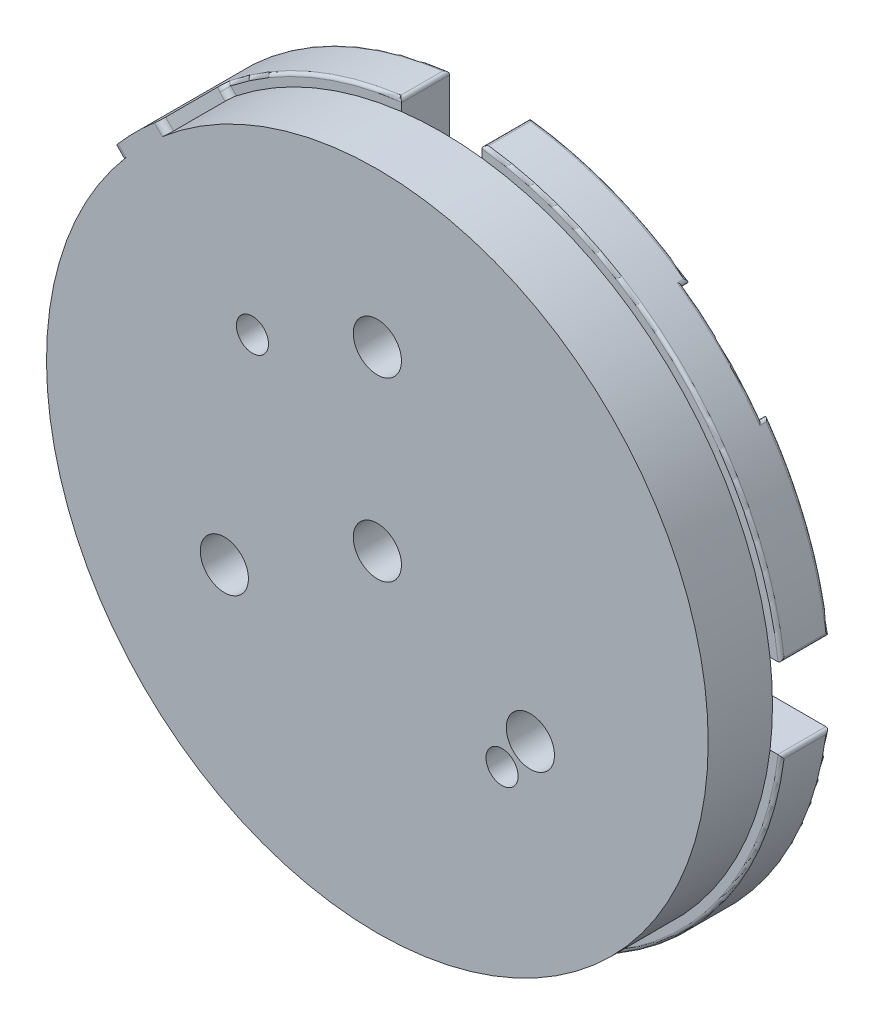
SolidWorks part; units mm, degrees
material "PE High Density"
ref_plane "Front Plane" through (0, 0, 0) normal (0, 0, 1) x (1, 0, 0)
ref_plane "Top Plane" through (0, 0, 0) normal (0, 1, 0) x (1, 0, 0)
ref_plane "Right Plane" through (0, 0, 0) normal (1, 0, 0) x (0, 0, -1)
sketch "Sketch1" plane through (0, 0, 0) normal (0, 0, 1) x (1, 0, 0)
  circle A0 centre (0, 0) radius 10.65
  dimension "D1" = 21.3
extrude "Boss-Extrude1" add sketch "Sketch1" along normal blind 1.5
sketch "Sketch2" plane through (0, 0, 1.5) normal (0, 0, 1) x (1, 0, 0)
  circle A0 centre (0, 0) radius 10.3
  dimension "D1" = 20.6
extrude "Boss-Extrude2" add sketch "Sketch2" along normal blind 2
sketch "Sketch3" plane through (0, 0, 0) normal (0, 0, -1) x (-1, 0, 0)
  circle A0 centre (0, 0) radius 3.75
  dimension "D1" = 7.5
extrude "Boss-Extrude3" add sketch "Sketch3" along normal blind 2.5
sketch "Sketch4" plane through (0, 0, -2.5) normal (0, 0, -1) x (-1, 0, 0)
  circle A0 centre (0, 0) radius 0.75
  dimension "D1" = 1.5
extrude "Cut-Extrude1" cut sketch "Sketch4" against normal through all
sketch "Sketch5" plane through (0, 0, 0) normal (0, 0, -1) x (-1, 0, 0)
  line L0 (0, 0) -> (3.8891, 3.8891) construction
  line L1 (0, 0) -> (0.0079, 0.0079) construction
  line L2 (0.0079, 0.0079) -> (-3.8812, -3.8812) construction
  circle A0 centre (0, 0) radius 5.5 construction
  circle A1 centre (0, 5.5) radius 0.75
  circle A2 centre (4.7631, -2.75) radius 0.75
  circle A3 centre (-4.7631, -2.75) radius 0.75
  circle A4 centre (3.8891, 3.8891) radius 0.5
  circle A5 centre (-3.8812, -3.8812) radius 0.5
  point P12 (0, 0)
  dimension "D1" = 11
  dimension "D2" = 1.5
  dimension "D4" = 1
  dimension "D5" = 1
  dimension "D3" = 3
extrude "Cut-Extrude2" cut sketch "Sketch5" against normal through all
sketch "Sketch6" plane through (0, 0, 0) normal (0, 0, -1) x (-1, 0, 0)
  line L0 (0, 0) -> (0, 10.65) construction
  line L1 (1.25, 0) -> (1.25, 10.65) construction
  line L2 (-1.25, 0) -> (-1.25, 10.65) construction
  line L3 (-1.25, 7.65) -> (1.25, 7.65)
  line L4 (-1.25, 7.65) -> (-1.25, 10.5764)
  line L5 (1.25, 7.65) -> (1.25, 10.5764)
  line L6 (7.65, 1.25) -> (10.5764, 1.25)
  line L7 (7.65, 1.25) -> (7.65, -1.25)
  line L8 (7.65, -1.25) -> (10.5764, -1.25)
  line L9 (1.25, -7.65) -> (1.25, -10.5764)
  line L10 (1.25, -7.65) -> (-1.25, -7.65)
  line L11 (-1.25, -7.65) -> (-1.25, -10.5764)
  line L12 (-7.65, -1.25) -> (-10.5764, -1.25)
  line L13 (-7.65, -1.25) -> (-7.65, 1.25)
  line L14 (-7.65, 1.25) -> (-10.5764, 1.25)
  arc A0 (1.25, 10.5764) -> (-1.25, 10.5764) centre (0, 0) ccw
  circle A1 centre (0, 0) radius 10.65 construction
  arc A2 (10.5764, -1.25) -> (10.5764, 1.25) centre (0, 0) ccw
  arc A3 (-1.25, -10.5764) -> (1.25, -10.5764) centre (0, 0) ccw
  arc A4 (-10.5764, 1.25) -> (-10.5764, -1.25) centre (0, 0) ccw
  point P28 (0, 0)
  dimension "D4" = 4
  dimension "D3" = 3
  dimension "D1" = 1.25
  dimension "D2" = 1.25
extrude "Cut-Extrude3" cut sketch "Sketch6" against normal up to surface (1.5 mm away) up to face at (10.3, 0, 1.5)
sketch "Sketch7" plane through (0, 0, 0) normal (0, 0, -1) x (-1, 0, 0)
  line L0 (0, 0) -> (-7.5452, 7.5452) construction
  line L1 (1.2021, 1.2021) -> (-6.3432, 8.7473) construction
  line L2 (-1.2021, -1.2021) -> (-8.7473, 6.3432) construction
  line L3 (-6.626, 4.2218) -> (-4.2218, 6.626)
  line L4 (-6.626, 4.2218) -> (-8.6509, 6.2468)
  line L5 (-4.2218, 6.626) -> (-6.2468, 8.6509)
  line L6 (0, 0) -> (2.2562, 2.2562) construction
  line L7 (6.626, -4.2218) -> (8.6509, -6.2468)
  line L8 (4.2218, -6.626) -> (6.626, -4.2218)
  line L9 (4.2218, -6.626) -> (6.2468, -8.6509)
  arc A0 (-6.2468, 8.6509) -> (-8.6509, 6.2468) centre (0, 0) ccw
  arc A1 (8.6509, -6.2468) -> (6.2468, -8.6509) centre (0, 0) cw
  dimension "D3" = 3
  dimension "D1" = 1.7
  dimension "D2" = 1.7
extrude "Cut-Extrude4" cut sketch "Sketch7" against normal blind 0.2
fillet "Fillet1" radius 0.3 1 edges at (-3.75, 0, -2.5)
fillet "Fillet2" radius 0.1 25 edges at (10.5764, -1.25, 0.75) (7.5307, -7.5307, 0) (1.25, -10.5764, 0.75) (7.5307, -7.5307, 1.5) (-1.25, -10.5764, 0.75) (-7.5307, -7.5307, 1.5) (-7.5307, 7.5307, 1.5) (-10.5764, 1.25, 0.75) (-10.5764, -1.25, 0.75) (-9.924, -3.8648, 0) (-3.8648, -9.924, 0) (-7.5307, 7.5307, 0) (9.924, 3.8648, 0) (3.8648, 9.924, 0) (-6.232, -8.6362, 0.1) (-7.5307, -7.5307, 0.2) (-8.6362, -6.232, 0.1) (-1.25, 10.5764, 0.75) (10.5764, 1.25, 0.75) (7.5307, 7.5307, 1.5) (1.25, 10.5764, 0.75) (6.232, 8.6362, 0.1) (7.5307, 7.5307, 0.2) (8.6362, 6.232, 0.1) (-3.75, 0, 0)
sketch "Sketch9" plane through (0, 0, 3.5) normal (0, 0, 1) x (1, 0, 0)
  line L0 (0, 0) -> (-7.5307, 7.5307) construction
  line L1 (-6.5417, 7.9559) -> (-6.7903, 8.2045)
  line L2 (-7.9559, 6.5417) -> (-8.2045, 6.7903)
  line L3 (-0.7071, -0.7071) -> (-8.2378, 6.8236) construction
  line L4 (0.7071, 0.7071) -> (-6.8236, 8.2378) construction
  arc A0 (-1.3628, 10.5624) -> (-10.5624, 1.3628) centre (0, 0) ccw construction
  arc A1 (-6.5417, 7.9559) -> (-7.9559, 6.5417) centre (0, 0) ccw
  arc A2 (-6.7903, 8.2045) -> (-8.2045, 6.7903) centre (0, 0) ccw
  dimension "D1" = 1
  dimension "D2" = 1
extrude "Boss-Extrude4" add sketch "Sketch9" against normal up to next
fillet "Fillet3" radius 0.2 6 edges at (-8.1792, 6.765, 1.4765) (-6.7786, 8.1928, 1.4549) (-8.0447, 6.6305, 1.5) (-8.0802, 6.666, 3.5) (-6.666, 8.0802, 3.5) (-6.6305, 8.0447, 1.5)
